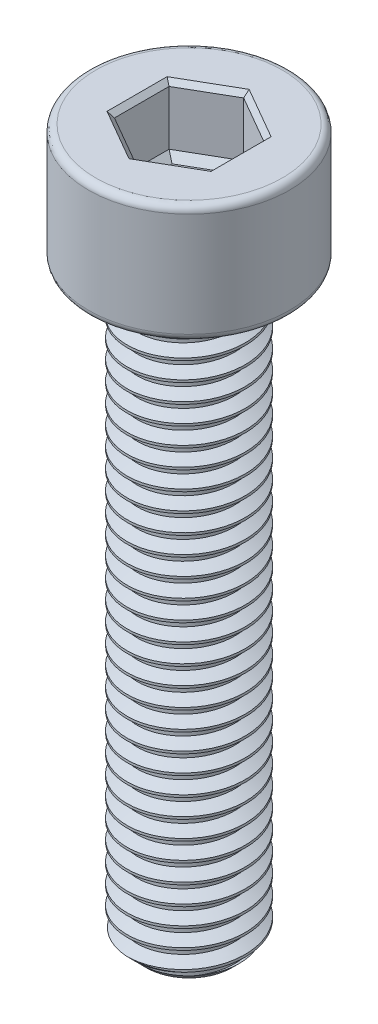
SolidWorks part; units mm, degrees
material "AISI Type A2 Tool Steel"
ref_plane "Front Plane" through (0, 0, 0) normal (0, 0, 1) x (1, 0, 0)
ref_plane "Top Plane" through (0, 0, 0) normal (0, 1, 0) x (1, 0, 0)
ref_plane "Right Plane" through (0, 0, 0) normal (1, 0, 0) x (0, 0, -1)
sketch "Sketch1" plane through (0, 0, 0) normal (0, 1, 0) x (1, 0, 0)
  circle A0 centre (0, 0) radius 2.5
  dimension "D1" = 5
extrude "Boss-Extrude1" add sketch "Sketch1" along normal blind 25
thread "Thread1" pitch 0.8 start angle 0, offset 1, length 0, pitch 0.8, diameter 5
ref_plane "Plane1" through (-2.5, 26, 0) normal (0, 0, 1) x (-1, 0, 0)
sketch "Thread Profile1" plane through (-2.5, 26, 0) normal (0, 0, 1) x (-1, 0, 0)
  line L0 (0, 0) -> (0, 0.8) construction
  line L11 (0, 0) -> (0, 0.7)
  line L12 (0, 0.7) -> (-0.433, 0.45)
  line L13 (-0.433, 0.45) -> (-0.433, 0.25)
  line L15 (-0.433, 0.25) -> (0, 0)
  line L17 (-0.433, 0.35) -> (0, 0.35) construction
  point P2 (0, 0)
  dimension "Pitch" = 0.8
  dimension "Profile_Angle" = 60
  dimension "Profile_Land" = 0.2
  dimension "Profile_Height" = 0.433
sketch "Sketch5" plane through (0, 25, 0) normal (0, 1, 0) x (1, 0, 0)
  circle A0 centre (0, 0) radius 4.25
  dimension "D1" = 8.5
extrude "Boss-Extrude2" add sketch "Sketch5" along normal blind 5
fillet "Fillet1" radius 0.3 2 edges at (0, 25, 4.25) (0, 30, 4.25)
sketch "Sketch6" plane through (0, 0, 0) normal (0, 0, 1) x (1, 0, 0)
  line L0 (0, 0) -> (0, 0.2882) construction
  line L1 (0, 0) -> (2.51, 0) construction
  line L2 (2.51, 0) -> (2.51, 0.7)
  line L3 (2.51, 0.7) -> (1.81, 0)
  line L4 (1.81, 0) -> (2.51, 0)
  dimension "D1" = 45
  dimension "D2" = 0.7
  dimension "D3" = 2.51
revolve "Cut-Revolve1" cut sketch "Sketch6" angle 360 about L0
sketch "Sketch7" plane through (0, 30, 0) normal (0, 1, 0) x (1, 0, 0)
  line L1 (0, 2.3094) -> (-2, 1.1547)
  line L2 (-2, 1.1547) -> (-2, -1.1547)
  line L3 (-2, -1.1547) -> (0, -2.3094)
  line L4 (0, -2.3094) -> (2, -1.1547)
  line L5 (2, -1.1547) -> (2, 1.1547)
  line L6 (2, 1.1547) -> (0, 2.3094)
  circle A0 centre (0, 0) radius 2 construction
  dimension "D1" = 4
extrude "Cut-Extrude1" cut sketch "Sketch7" against normal blind 2.5
chamfer "Chamfer1" distance 0.2 angle 45 6 edges at (-2, 30, 0) (-1, 30, 1.7321) (1, 30, 1.7321) (2, 30, 0) (1, 30, -1.7321) (-1, 30, -1.7321)
sketch "Sketch8" plane through (0, 27.5, 0) normal (0, 1, 0) x (1, 0, 0)
  line L1 (0, 2.3094) -> (-2, 1.1547)
  line L2 (-2, 1.1547) -> (-2, -1.1547)
  line L3 (-2, -1.1547) -> (0, -2.3094)
  line L4 (0, -2.3094) -> (2, -1.1547)
  line L5 (2, -1.1547) -> (2, 1.1547)
  line L6 (2, 1.1547) -> (0, 2.3094)
  circle A0 centre (0, 0) radius 2 construction
extrude "Cut-Extrude2" cut sketch "Sketch8" against normal blind 0.3 draft 45
